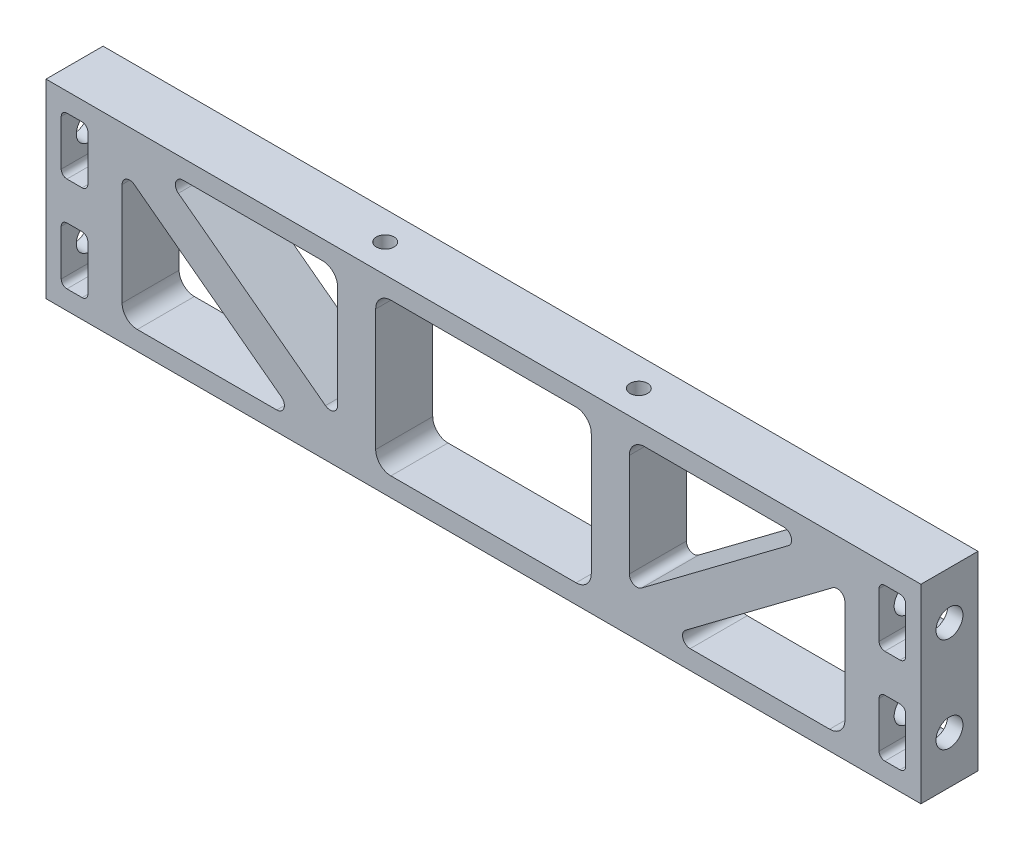
SolidWorks part; units mm, degrees
material "PE High Density"
ref_plane "Front Plane" through (0, 0, 0) normal (0, 0, 1) x (1, 0, 0)
ref_plane "Top Plane" through (0, 0, 0) normal (0, 1, 0) x (1, 0, 0)
ref_plane "Right Plane" through (0, 0, 0) normal (1, 0, 0) x (0, 0, -1)
sketch "Sketch1" plane through (0, 0, 0) normal (0, 0, 1) x (1, 0, 0)
  line L0 (-24.3417, 15.875) -> (-24.3417, -15.875) construction
  line L1 (-73.025, 15.875) -> (73.025, 15.875)
  line L2 (-73.025, 15.875) -> (-73.025, -15.875)
  line L3 (-73.025, -15.875) -> (73.025, -15.875)
  line L4 (73.025, 15.875) -> (73.025, -15.875)
  line L5 (-73.025, 15.875) -> (73.025, -15.875) construction
  line L6 (-73.025, -15.875) -> (73.025, 15.875) construction
  line L7 (24.3417, 15.875) -> (24.3417, -15.875) construction
  line L9 (-69.85, -12.7) -> (-27.5167, 12.7) construction
  line L10 (-69.85, -12.7) -> (-69.85, 12.7) construction
  line L11 (-64.3071, -11.2256) -> (-29.9209, 9.4061)
  line L12 (-73.025, -15.875) -> (-24.3417, -15.875)
  line L13 (-73.025, -15.875) -> (-73.025, 15.875)
  line L14 (-73.025, 15.875) -> (-24.3417, 15.875)
  line L15 (-24.3417, -15.875) -> (-24.3417, 15.875) construction
  line L16 (-69.85, 12.7) -> (-27.5167, 12.7) construction
  line L17 (-27.5167, -12.7) -> (-27.5167, 12.7) construction
  line L18 (-69.85, -12.7) -> (-27.5167, -12.7) construction
  line L19 (-67.4457, -9.4061) -> (-33.0595, 11.2256)
  line L20 (-69.0332, -14.0613) -> (-26.6999, 11.3387) construction
  line L21 (-69.85, -8.0448) -> (-69.85, 11.1125)
  line L22 (-70.6668, -11.3387) -> (-28.3334, 14.0613) construction
  line L23 (-68.2625, 12.7) -> (-33.4679, 12.7)
  line L24 (-63.8988, -12.7) -> (-29.1042, -12.7)
  line L25 (-27.5167, -11.1125) -> (-27.5167, 8.0448)
  line L26 (-15.6238, -11.2256) -> (18.7624, 9.4061)
  line L27 (-18.7624, -9.4061) -> (15.6238, 11.2256)
  line L28 (-21.1667, -8.0448) -> (-21.1667, 11.1125)
  line L29 (-19.5792, 12.7) -> (15.2154, 12.7)
  line L30 (-15.2154, -12.7) -> (19.5792, -12.7)
  line L31 (21.1667, -11.1125) -> (21.1667, 8.0448)
  line L32 (-21.1667, -12.7) -> (21.1667, 12.7) construction
  line L33 (-21.1667, -12.7) -> (-21.1667, 12.7) construction
  line L34 (-21.1667, 12.7) -> (21.1667, 12.7) construction
  line L35 (21.1667, -12.7) -> (21.1667, 12.7) construction
  line L36 (-21.1667, -12.7) -> (21.1667, -12.7) construction
  line L37 (33.0595, -11.2256) -> (67.4457, 9.4061)
  line L38 (29.9209, -9.4061) -> (64.3071, 11.2256)
  line L39 (27.5167, -8.0448) -> (27.5167, 11.1125)
  line L40 (29.1042, 12.7) -> (63.8988, 12.7)
  line L41 (33.4679, -12.7) -> (68.2625, -12.7)
  line L42 (69.85, -11.1125) -> (69.85, 8.0448)
  line L43 (27.5167, -12.7) -> (69.85, 12.7) construction
  line L44 (27.5167, -12.7) -> (27.5167, 12.7) construction
  line L45 (27.5167, 12.7) -> (69.85, 12.7) construction
  line L46 (69.85, -12.7) -> (69.85, 12.7) construction
  line L47 (27.5167, -12.7) -> (69.85, -12.7) construction
  line L59 (-64.3071, -11.2256) -> (-15.6238, -11.2256) construction
  line L60 (-69.85, 15.875) -> (-69.85, -15.875)
  arc A0 (-33.4679, 12.7) -> (-33.0595, 11.2256) centre (-33.4679, 11.9062) cw
  arc A1 (-69.85, -8.0448) -> (-67.4457, -9.4061) centre (-68.2625, -8.0448) ccw
  arc A2 (-69.85, 11.1125) -> (-68.2625, 12.7) centre (-68.2625, 11.1125) cw
  arc A3 (-27.5167, 8.0448) -> (-29.9209, 9.4061) centre (-29.1042, 8.0448) ccw
  arc A4 (-63.8988, -12.7) -> (-64.3071, -11.2256) centre (-63.8988, -11.9062) cw
  arc A5 (-27.5167, -11.1125) -> (-29.1042, -12.7) centre (-29.1042, -11.1125) cw
  arc A6 (15.2154, 12.7) -> (15.6238, 11.2256) centre (15.2154, 11.9062) cw
  arc A7 (-21.1667, -8.0448) -> (-18.7624, -9.4061) centre (-19.5792, -8.0448) ccw
  arc A8 (-21.1667, 11.1125) -> (-19.5792, 12.7) centre (-19.5792, 11.1125) cw
  arc A9 (21.1667, 8.0448) -> (18.7624, 9.4061) centre (19.5792, 8.0448) ccw
  arc A10 (-15.2154, -12.7) -> (-15.6238, -11.2256) centre (-15.2154, -11.9062) cw
  arc A11 (21.1667, -11.1125) -> (19.5792, -12.7) centre (19.5792, -11.1125) cw
  arc A12 (63.8988, 12.7) -> (64.3071, 11.2256) centre (63.8988, 11.9062) cw
  arc A13 (27.5167, -8.0448) -> (29.9209, -9.4061) centre (29.1042, -8.0448) ccw
  arc A14 (27.5167, 11.1125) -> (29.1042, 12.7) centre (29.1042, 11.1125) cw
  arc A15 (69.85, 8.0448) -> (67.4457, 9.4061) centre (68.2625, 8.0448) ccw
  arc A16 (33.4679, -12.7) -> (33.0595, -11.2256) centre (33.4679, -11.9062) cw
  arc A17 (69.85, -11.1125) -> (68.2625, -12.7) centre (68.2625, -11.1125) cw
  point P0 (0, 0)
  point P26 (-30.6022, 12.7)
  point P29 (-69.85, -10.8487)
  point P35 (-27.5167, 10.8487)
  point P38 (-66.7645, -12.7)
  dimension "D7" = 0.7937
  dimension "D8" = 1.5875
  dimension "D9" = 1.5875
  dimension "D10" = 1.5875
  dimension "D11" = 0.7937
  dimension "D12" = 1.5875
  dimension "D1" = 31.75
  dimension "CrossBraceLength" = 146.05
  dimension "D4" = 48.6833
  dimension "D14" = 48.6833
  dimension "D6" = 3.175
  dimension "D2" = 1.5875
  dimension "D5" = 1.5875
  dimension "D3" = 3
  dimension "D13" = 3
extrude "Boss-Extrude1" [suppressed] add sketch "Sketch1" along normal blind 9.525
sketch "Sketch2" plane through (0, 0, 0) normal (0, 0, 1) x (1, 0, 0)
  line L0 (-63.5, 15.875) -> (-63.5, -15.875) construction
  line L1 (-73.025, 15.875) -> (73.025, 15.875)
  line L2 (-73.025, 15.875) -> (-73.025, -15.875)
  line L3 (-73.025, -15.875) -> (73.025, -15.875)
  line L4 (73.025, 15.875) -> (73.025, -15.875)
  line L5 (-73.025, 15.875) -> (73.025, -15.875) construction
  line L6 (-73.025, -15.875) -> (73.025, 15.875) construction
  line L7 (0, 15.875) -> (0, -15.875) construction
  line L8 (-63.5, -15.875) -> (-63.5, 15.875) construction
  line L9 (63.5, 15.875) -> (63.5, -15.875) construction
  line L10 (-21.1667, 15.875) -> (-21.1667, -15.875) construction
  line L11 (-73.025, 0) -> (73.025, 0) construction
  line L12 (21.1667, 15.875) -> (21.1667, -15.875) construction
  line L14 (-63.5, -15.875) -> (-63.5, 15.875) construction
  line L15 (-63.5, 15.875) -> (-21.1667, 15.875)
  line L19 (-63.5, 15.875) -> (-21.1667, -15.875) construction
  line L20 (-63.5, -15.875) -> (-21.1667, -15.875)
  line L21 (-21.1667, 15.875) -> (-63.5, 15.875)
  line L22 (-63.5, -15.875) -> (-21.1667, -15.875)
  line L23 (-63.5, -15.875) -> (-63.5, 15.875) construction
  line L27 (-63.5, 15.875) -> (-21.1667, -15.875) construction
  line L28 (-50.927, 10.414) -> (-26.3737, -8.001)
  line L29 (-60.325, -10.16) -> (-60.325, 6.985)
  line L48 (-57.785, -12.7) -> (-34.5017, -12.7)
  line L61 (-69.5325, 12.7) -> (-66.9925, 12.7)
  line L62 (-70.485, 11.7475) -> (-70.485, 4.1275)
  line L63 (-69.5325, 3.175) -> (-66.9925, 3.175)
  line L64 (-66.04, 11.7475) -> (-66.04, 4.1275)
  line L65 (-70.485, 12.7) -> (-66.04, 3.175) construction
  line L66 (-70.485, 3.175) -> (-66.04, 12.7) construction
  line L67 (-68.2625, 15.875) -> (-68.2625, -15.875) construction
  line L68 (-68.2625, 3.175) -> (-68.2625, 11.967) construction
  line L69 (-70.485, 7.9375) -> (-66.04, 7.9375) construction
  line L70 (-70.485, -7.9375) -> (-66.04, -7.9375) construction
  line L71 (-68.2625, -3.175) -> (-68.2625, -11.967) construction
  line L72 (-70.485, -3.175) -> (-66.04, -12.7) construction
  line L73 (-70.485, -12.7) -> (-66.04, -3.175) construction
  line L74 (-66.04, -11.7475) -> (-66.04, -4.1275)
  line L75 (-69.5325, -3.175) -> (-66.9925, -3.175)
  line L76 (-70.485, -11.7475) -> (-70.485, -4.1275)
  line L77 (-69.5325, -12.7) -> (-66.9925, -12.7)
  line L78 (-58.293, 8.001) -> (-33.7397, -10.414)
  line L79 (70.485, -12.7) -> (66.04, -3.175) construction
  line L80 (70.485, -3.175) -> (66.04, -12.7) construction
  line L81 (68.2625, -3.175) -> (68.2625, -11.967) construction
  line L82 (70.485, -7.9375) -> (66.04, -7.9375) construction
  line L83 (70.485, 7.9375) -> (66.04, 7.9375) construction
  line L84 (68.2625, 3.175) -> (68.2625, 11.967) construction
  line L85 (68.2625, 15.875) -> (68.2625, -15.875) construction
  line L86 (70.485, 3.175) -> (66.04, 12.7) construction
  line L87 (70.485, 12.7) -> (66.04, 3.175) construction
  line L88 (69.5325, -12.7) -> (66.9925, -12.7)
  line L89 (70.485, -11.7475) -> (70.485, -4.1275)
  line L90 (69.5325, -3.175) -> (66.9925, -3.175)
  line L91 (66.04, -11.7475) -> (66.04, -4.1275)
  line L92 (66.04, 11.7475) -> (66.04, 4.1275)
  line L93 (69.5325, 3.175) -> (66.9925, 3.175)
  line L94 (70.485, 11.7475) -> (70.485, 4.1275)
  line L95 (69.5325, 12.7) -> (66.9925, 12.7)
  line L96 (73.025, 15.875) -> (73.025, -15.875)
  line L97 (-63.5, 15.875) -> (-24.3417, 15.875)
  line L99 (-60.325, -15.875) -> (-60.325, 15.875) construction
  line L102 (-24.3417, 10.16) -> (-24.3417, -6.985)
  line L104 (-50.165, 12.7) -> (-26.8817, 12.7)
  line L105 (24.3417, 10.16) -> (24.3417, -6.985)
  line L106 (-24.3417, 15.875) -> (-24.3417, -15.875) construction
  line L107 (50.165, 12.7) -> (26.8817, 12.7)
  line L108 (50.927, 10.414) -> (26.3737, -8.001)
  line L109 (57.785, -12.7) -> (34.5017, -12.7)
  line L110 (58.293, 8.001) -> (33.7397, -10.414)
  line L111 (60.325, -10.16) -> (60.325, 6.985)
  line L112 (0, -15.875) -> (0, -12.7)
  line L114 (-15.4517, 12.7) -> (15.4517, 12.7)
  line L115 (-17.9917, 10.16) -> (-17.9917, -10.16)
  line L116 (-15.4517, -12.7) -> (15.4517, -12.7)
  line L117 (17.9917, 10.16) -> (17.9917, -10.16)
  line L118 (-17.9917, 12.7) -> (17.9917, -12.7) construction
  line L119 (-17.9917, -12.7) -> (17.9917, 12.7) construction
  arc A36 (-66.9925, 3.175) -> (-66.04, 4.1275) centre (-66.9925, 4.1275) ccw
  arc A37 (-66.9925, 12.7) -> (-66.04, 11.7475) centre (-66.9925, 11.7475) cw
  arc A38 (-69.5325, 3.175) -> (-70.485, 4.1275) centre (-69.5325, 4.1275) cw
  arc A39 (-69.5325, 12.7) -> (-70.485, 11.7475) centre (-69.5325, 11.7475) ccw
  arc A40 (-69.5325, -12.7) -> (-70.485, -11.7475) centre (-69.5325, -11.7475) cw
  arc A41 (-69.5325, -3.175) -> (-70.485, -4.1275) centre (-69.5325, -4.1275) ccw
  arc A42 (-66.9925, -12.7) -> (-66.04, -11.7475) centre (-66.9925, -11.7475) ccw
  arc A43 (-66.9925, -3.175) -> (-66.04, -4.1275) centre (-66.9925, -4.1275) cw
  arc A44 (66.9925, -3.175) -> (66.04, -4.1275) centre (66.9925, -4.1275) ccw
  arc A45 (66.9925, -12.7) -> (66.04, -11.7475) centre (66.9925, -11.7475) cw
  arc A46 (69.5325, -3.175) -> (70.485, -4.1275) centre (69.5325, -4.1275) cw
  arc A47 (69.5325, -12.7) -> (70.485, -11.7475) centre (69.5325, -11.7475) ccw
  arc A48 (69.5325, 12.7) -> (70.485, 11.7475) centre (69.5325, 11.7475) cw
  arc A49 (69.5325, 3.175) -> (70.485, 4.1275) centre (69.5325, 4.1275) ccw
  arc A50 (66.9925, 12.7) -> (66.04, 11.7475) centre (66.9925, 11.7475) ccw
  arc A51 (66.9925, 3.175) -> (66.04, 4.1275) centre (66.9925, 4.1275) cw
  arc A52 (-57.785, -12.7) -> (-60.325, -10.16) centre (-57.785, -10.16) cw
  arc A53 (-60.325, 6.985) -> (-58.293, 8.001) centre (-59.055, 6.985) cw
  arc A54 (-34.5017, -12.7) -> (-33.7397, -10.414) centre (-34.5017, -11.43) ccw
  arc A55 (-26.8817, 12.7) -> (-24.3417, 10.16) centre (-26.8817, 10.16) cw
  arc A56 (-26.3737, -8.001) -> (-24.3417, -6.985) centre (-25.6117, -6.985) ccw
  arc A57 (-50.927, 10.414) -> (-50.165, 12.7) centre (-50.165, 11.43) cw
  arc A58 (26.3737, -8.001) -> (24.3417, -6.985) centre (25.6117, -6.985) cw
  arc A59 (26.8817, 12.7) -> (24.3417, 10.16) centre (26.8817, 10.16) ccw
  arc A60 (50.927, 10.414) -> (50.165, 12.7) centre (50.165, 11.43) ccw
  arc A61 (57.785, -12.7) -> (60.325, -10.16) centre (57.785, -10.16) ccw
  arc A62 (34.5017, -12.7) -> (33.7397, -10.414) centre (34.5017, -11.43) cw
  arc A63 (60.325, 6.985) -> (58.293, 8.001) centre (59.055, 6.985) ccw
  arc A64 (-15.4517, -12.7) -> (-17.9917, -10.16) centre (-15.4517, -10.16) cw
  arc A65 (-17.9917, 10.16) -> (-15.4517, 12.7) centre (-15.4517, 10.16) cw
  arc A66 (17.9917, 10.16) -> (15.4517, 12.7) centre (15.4517, 10.16) ccw
  arc A67 (17.9917, -10.16) -> (15.4517, -12.7) centre (15.4517, -10.16) cw
  point P16 (-68.2625, 7.9375)
  point P18 (-65.405, 13.335)
  point P19 (-23.0717, -18.415)
  point P24 (-63.5, 12.7)
  point P26 (-24.3417, 12.7)
  point P34 (-61.595, 18.415)
  point P36 (-19.2617, -13.335)
  point P65 (0, 0)
  point P124 (-68.2625, -7.9375)
  point P168 (68.2625, -7.9375)
  point P169 (68.2625, 7.9375)
  dimension "D19" = 0.9525
  dimension "D20" = 0.9525
  dimension "D21" = 0.9525
  dimension "D22" = 0.9525
  dimension "D6" = 2.54
  dimension "D8" = 1.27
  dimension "D9" = 1.27
  dimension "D11" = 2.54
  dimension "D12" = 1.27
  dimension "D13" = 1.27
  dimension "D16" = 2.54
  dimension "D1" = 146.05
  dimension "D2" = 31.75
  dimension "D3" = 9.525
  dimension "D17" = 4.445
  dimension "D18" = 9.525
  dimension "D23" = 4.7625
  dimension "D24" = 7.9375
  dimension "D4" = 42.3333
  dimension "D5" = 42.3333
  dimension "D14" = 3.175
  dimension "D15" = 35.9833
  dimension "D7" = 3.175
  dimension "D10" = 3.175
extrude "Boss-Extrude2" add sketch "Sketch2" along normal blind 9.525 contours L4 L1 L2 L3 region at (-68.2625, 14.3804, 0)
sketch "Sketch3" plane through (-73.025, 0, 0) normal (-1, 0, 0) x (0, 0, 1)
  line L0 (9.525, 15.875) -> (0, 15.875) construction
  line L1 (0, 0) -> (9.525, 0) construction
  line L2 (9.525, 15.875) -> (9.525, -15.875) construction
  line L3 (4.7625, -15.875) -> (4.7625, 15.875) construction
  line L4 (9.525, -15.875) -> (0, -15.875) construction
  circle A0 centre (4.7625, 7.9375) radius 2.2479
  dimension "D2" = 4.4958
  dimension "D1" = 7.9375
extrude "Cut-Extrude1" cut sketch "Sketch3" against normal blind 11.1125
mirror "Mirror1" about plane through (0, 0, 0) normal (1, 0, 0) of "Cut-Extrude1" second plane through (0, 0, 0) second plane normal (0, 1, 0)
sketch "Sketch4" plane through (0, 15.875, 0) normal (0, 1, 0) x (1, 0, 0)
  line L2 (17.9917, -9.525) -> (17.9917, 0) construction
  line L3 (17.9917, -9.525) -> (17.9917, 0) construction
  line L4 (73.025, 0) -> (-73.025, 0)
  line L5 (-73.025, 0) -> (-73.025, -9.525)
  line L6 (-73.025, -9.525) -> (73.025, -9.525)
  line L7 (73.025, -9.525) -> (73.025, 0)
  line L8 (73.025, 0) -> (-73.025, 0) construction
  line L9 (-73.025, 0) -> (-73.025, -9.525) construction
  line L10 (-73.025, -9.525) -> (73.025, -9.525) construction
  line L11 (73.025, -9.525) -> (73.025, 0) construction
  line L12 (-17.9917, -9.525) -> (-17.9917, 0) construction
  line L13 (-17.9917, -9.525) -> (-17.9917, 0) construction
  line L14 (-24.3417, -9.525) -> (-24.3417, 0) construction
  line L15 (-24.3417, -9.525) -> (-24.3417, 0) construction
  line L16 (24.3417, -9.525) -> (24.3417, 0) construction
  line L17 (24.3417, -9.525) -> (24.3417, 0) construction
  line L18 (24.3417, -9.525) -> (17.9917, 0) construction
  line L19 (17.9917, -9.525) -> (24.3417, 0) construction
  circle A0 centre (21.1667, -4.7625) radius 1.4732
  dimension "D2" = 2.9464
  dimension "D1" = 0
extrude "Cut-Extrude2" cut sketch "Sketch4" against normal blind 12.7 contours A0
mirror "Mirror2" about plane through (0, 0, 0) normal (0, 1, 0) of "Cut-Extrude2" second plane through (0, 0, 0) second plane normal (1, 0, 0)
equation "\"Plate Width\" = 3.5in"
equation "\"Plate Thickness\" = 0.375in"
equation "\"Num holes\" = 4"
equation "\"Plate Height\" = 1.25in"
equation "\"Top Plate Width\" = 4.5in"
equation "\"Plate Clearance Hole Diameter\" = 0.125in"
equation "\"Plate Tap Hole Diameter\" = 0.116in"
equation "\"Bottom Plate Length\" = 6.5in"
equation "\"CrossBraceLength@Sketch1\" = \"Bottom Plate Length\" - 2 * \"Plate Thickness\""
equation "\"D1@Sketch1\"=\"Plate Height\""
equation "\"num_triangle_holes\"= 3"
equation "\"D3@Sketch1\"=\"num_triangle_holes\""
equation "\"D4@Sketch1\"=( \"Bottom Plate Length\" - 2 * \"Plate Thickness\" ) / \"num_triangle_holes\""
equation "\"BorderThickness\"= 0.125"
equation "\"D6@Sketch1\"=\"BorderThickness\""
equation "\"D2@Sketch1\"=\"BorderThickness\"/2"
equation "\"D9@Sketch1\"=\"BorderThickness\"/2"
equation "\"D8@Sketch1\"=\"BorderThickness\"/2"
equation "\"D7@Sketch1\"=\"BorderThickness\"/4"
equation "\"D10@Sketch1\"=\"BorderThickness\"/2"
equation "\"D11@Sketch1\"=\"BorderThickness\"/4"
equation "\"D12@Sketch1\"=\"BorderThickness\"/2"
equation "\"D13@Sketch1\"=\"num_triangle_holes\""
equation "\"D14@Sketch1\"=( \"Bottom Plate Length\" - 2 * \"Plate Thickness\" ) / \"num_triangle_holes\""
equation "\"D1@Boss-Extrude1\"=\"Plate Thickness\""
equation "\"D1@Sketch2\"=\"Bottom Plate Length\" - 2 * \"Plate Thickness\""
equation "\"D2@Sketch2\"=\"Plate Height\""
equation "\"wall_thickness\"= 0.375"
equation "\"D3@Sketch2\"=\"wall_thickness\""
equation "\"D1@Boss-Extrude2\"=\"Plate Thickness\""
equation "\"D23@Sketch2\"=\"wall_thickness\"/2"
equation "\"D24@Sketch2\"=\"Plate Height\"/4"
equation "\"Number Eight Clearance Size\" = 0.177in"
equation "\"D1@Sketch3\"=\"Plate Height\" / 4"
equation "\"D2@Sketch3\"=\"Number Eight Clearance Size\""
equation "\"D1@Cut-Extrude1\"=(0.75 - \"Plate Thickness\") + 0.0625"
equation "\"D4@Sketch2\"=( ( \"Bottom Plate Length\" - 2 * \"Plate Thickness\" ) - \"Plate Thickness\" * 2 ) /3"
equation "\"D5@Sketch2\"=( ( \"Bottom Plate Length\" - 2 * \"Plate Thickness\" ) - \"Plate Thickness\" * 2 ) /3"
equation "\"D14@Sketch2\"=\"BorderThickness\""
equation "\"D15@Sketch2\"=( ( ( \"Bottom Plate Length\" - 2 * \"Plate Thickness\" ) - \"Plate Thickness\" * 2 ) /3 ) - \"BorderThickness\"*2"
